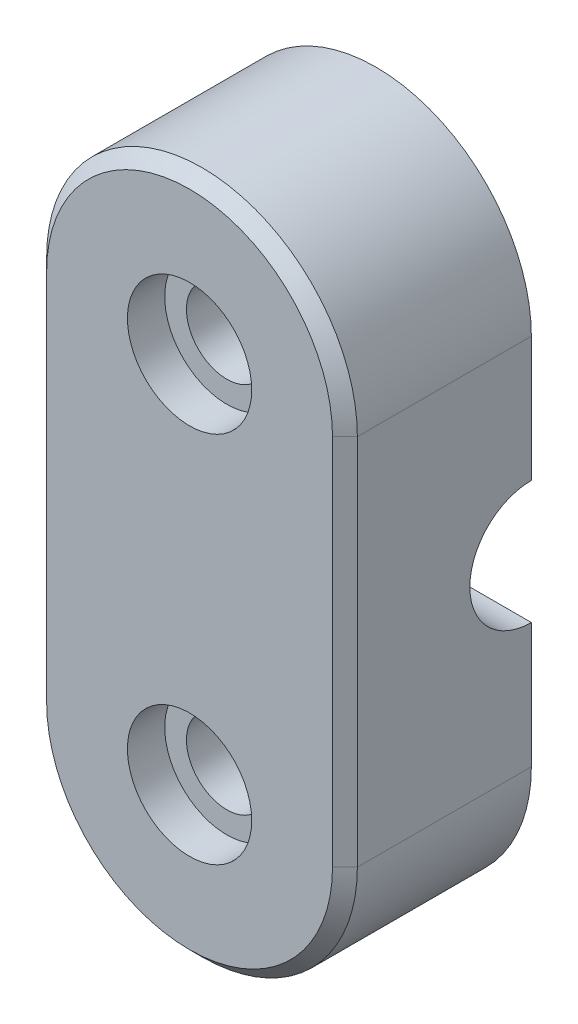
SolidWorks part; units mm, degrees
ref_plane "Front Plane" through (0, 0, 0) normal (0, 0, 1) x (1, 0, 0)
ref_plane "Top Plane" through (0, 0, 0) normal (0, 1, 0) x (1, 0, 0)
ref_plane "Right Plane" through (0, 0, 0) normal (1, 0, 0) x (0, 0, -1)
sketch "Sketch1" plane through (0, 0, 0) normal (0, 0, 1) x (1, 0, 0)
  line L12 (-12.5, 15) -> (-12.5, -15)
  line L13 (12.5, 15) -> (12.5, -15)
  arc A0 (12.5, 15) -> (-12.5, 15) centre (0, 15) ccw construction
  arc A1 (-12.5, -15) -> (12.5, -15) centre (0, -15) ccw construction
  arc A2 (12.5, 15) -> (-12.5, 15) centre (0, 15) ccw
  arc A3 (-12.5, -15) -> (12.5, -15) centre (0, -15) ccw
  circle A4 centre (0, 15) radius 3.25 construction
  circle A5 centre (0, -15) radius 3.25 construction
  circle A6 centre (0, 15) radius 3.25
  circle A7 centre (0, -15) radius 3.25
extrude "Boss-Extrude1" add sketch "Sketch1" along normal blind 15 contours A3 A7 | A2 A6 region at (0, 0, 0)
sketch "Sketch2" plane through (12.5, 0, 0) normal (1, 0, 0) x (0, 0, -1)
  circle A0 centre (0, 0) radius 4.95
  arc A2 (0, -4.95) -> (0, 4.95) centre (0, 0) ccw construction
extrude "Cut-Extrude1" cut sketch "Sketch2" against normal up to next
chamfer "Chamfer1" distance 1 angle 45 4 edges at (0, -27.5, 15) (0, 27.5, 15) (-12.5, 0, 15) (12.5, 0, 15)
sketch "Sketch3" plane through (0, 0, 15) normal (0, 0, 1) x (1, 0, 0)
  circle A0 centre (0, 15) radius 5
  circle A1 centre (0, -15) radius 5
  dimension "D1" = 10
extrude "Cut-Extrude2" cut sketch "Sketch3" against normal blind 3
sketch "Sketch5" plane through (0, 0, 0) normal (1, 0, 0) x (0, 0, -1)
  line L0 (0, 4.95) -> (0, -4.95)
  circle A0 centre (0, 0) radius 4.95
  circle A1 centre (0, 0) radius 4.5
  arc A2 (0, -4.5) -> (0, 4.5) centre (0, 0) ccw construction
  arc A4 (0, 4.95) -> (0, -4.95) centre (0, 0) ccw construction
extrude "Boss-Extrude2" add sketch "Sketch5" along normal mid plane 1.9 contours A1 L0 A0 region at (0, 4.725, 0.1107)
